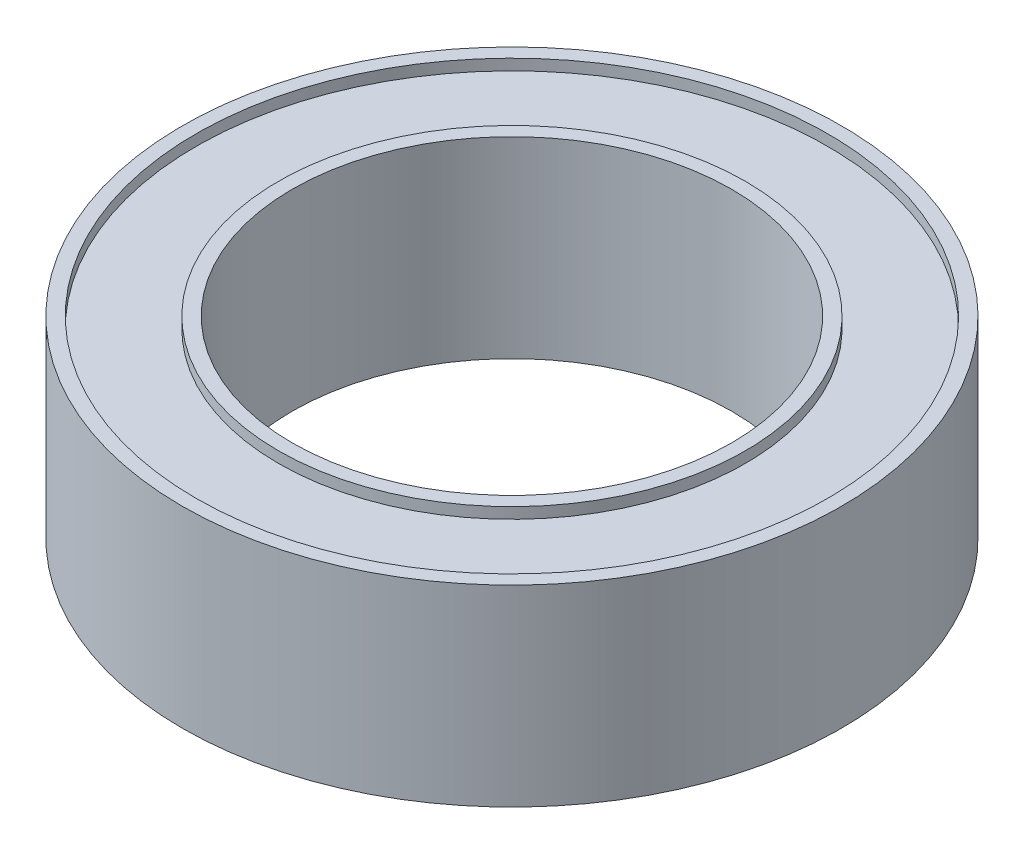
SolidWorks part; units mm, degrees
material "1060 Alloy"
ref_plane "Front Plane" through (0, 0, 0) normal (0, 0, 1) x (1, 0, 0)
ref_plane "Top Plane" through (0, 0, 0) normal (0, 1, 0) x (1, 0, 0)
ref_plane "Right Plane" through (0, 0, 0) normal (1, 0, 0) x (0, 0, -1)
sketch "Sketch1" plane through (0, 0, 0) normal (0, 1, 0) x (1, 0, 0)
  circle A0 centre (0, 0) radius 4
  circle A1 centre (0, 0) radius 6
  dimension "D1" = 8
  dimension "D2" = 12
extrude "Boss-Extrude1" add sketch "Sketch1" along normal blind 3.5
sketch "Sketch2" plane through (0, 3.5, 0) normal (0, 1, 0) x (1, 0, 0)
  circle A0 centre (0, 0) radius 4.25
  circle A1 centre (0, 0) radius 5.75
  circle A2 centre (0, 0) radius 4 construction
  circle A3 centre (0, 0) radius 6 construction
  dimension "D1" = 0.25
  dimension "D2" = 0.25
extrude "Cut-Extrude1" cut sketch "Sketch2" against normal blind 0.2
extrude "Cut-Extrude2" cut sketch "Sketch2<2>" along normal blind 0.2 from surface starting at face at (0, 0, 6)
sketch "Sketch2<2>" plane through (0, 3.5, 0) normal (0, 1, 0) x (1, 0, 0) same geometry as "Sketch2"
